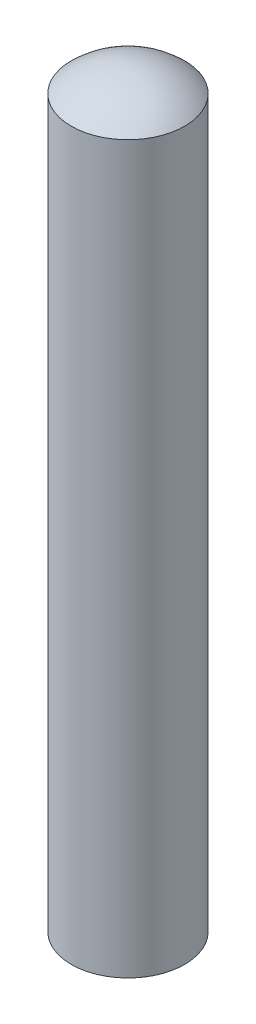
SolidWorks part; units mm, degrees
ref_plane "Front Plane" through (0, 0, 0) normal (0, 0, 1) x (1, 0, 0)
ref_plane "Top Plane" through (0, 0, 0) normal (0, 1, 0) x (1, 0, 0)
ref_plane "Right Plane" through (0, 0, 0) normal (1, 0, 0) x (0, 0, -1)
sketch "Sketch1" plane through (0, 0, 0) normal (0, 0, 1) x (1, 0, 0)
  line L0 (0, 0) -> (-12.5, 0)
  line L1 (-12.5, 0) -> (-12.5, 30)
  line L2 (-12.5, 30) -> (-12.5, 100)
  line L3 (-12.5, 100) -> (-12.5, 160)
  line L4 (-12.5, 160) -> (0, 160)
  line L5 (0, 160) -> (0, 0) construction
  line L6 (0, 0) -> (0, 160)
  dimension "D1" = 160
  dimension "D2" = 12.5
  dimension "D3" = 60
  dimension "D4" = 30
revolve "Revolve1" add sketch "Sketch1" angle 360 about L5
cosmetic thread "Cosmetic Thread2" parameters "D1"=30, "D2"=23.38
cosmetic thread "Cosmetic Thread3" parameters "D1"=60, "D2"=23.38
dome "Dome1" faces to dome 1 distance 5 reverse direction no elliptical dome no face at (0, 160, 12.5) parameters "D1"=5
